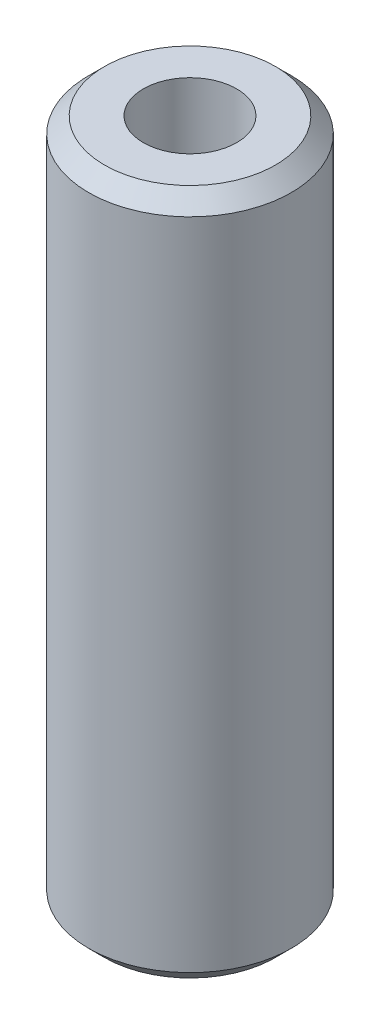
SolidWorks part; units mm, degrees
ref_plane "Front Plane" through (0, 0, 0) normal (0, 0, 1) x (1, 0, 0)
ref_plane "Top Plane" through (0, 0, 0) normal (0, 1, 0) x (1, 0, 0)
ref_plane "Right Plane" through (0, 0, 0) normal (1, 0, 0) x (0, 0, -1)
sketch "Sketch1" plane through (0, 0, 0) normal (0, 1, 0) x (1, 0, 0)
  circle A0 centre (0, 0) radius 35
  dimension "SHAFT_OD" = 70
extrude "Boss-Extrude1" add sketch "Sketch1" along normal blind 236.9822
sketch "Sketch2" plane through (0, 0, 0) normal (0, 1, 0) x (1, 0, 0)
  circle A0 centre (0, 0) radius 16.1123
  dimension "BORE_D" = 32.2246
extrude "Cut-Extrude1" cut sketch "Sketch2" along normal through all
chamfer "Chamfer1" distance 5.4903 angle 45 2 edges at (0, 236.9822, 35) (0, 0, 35)
